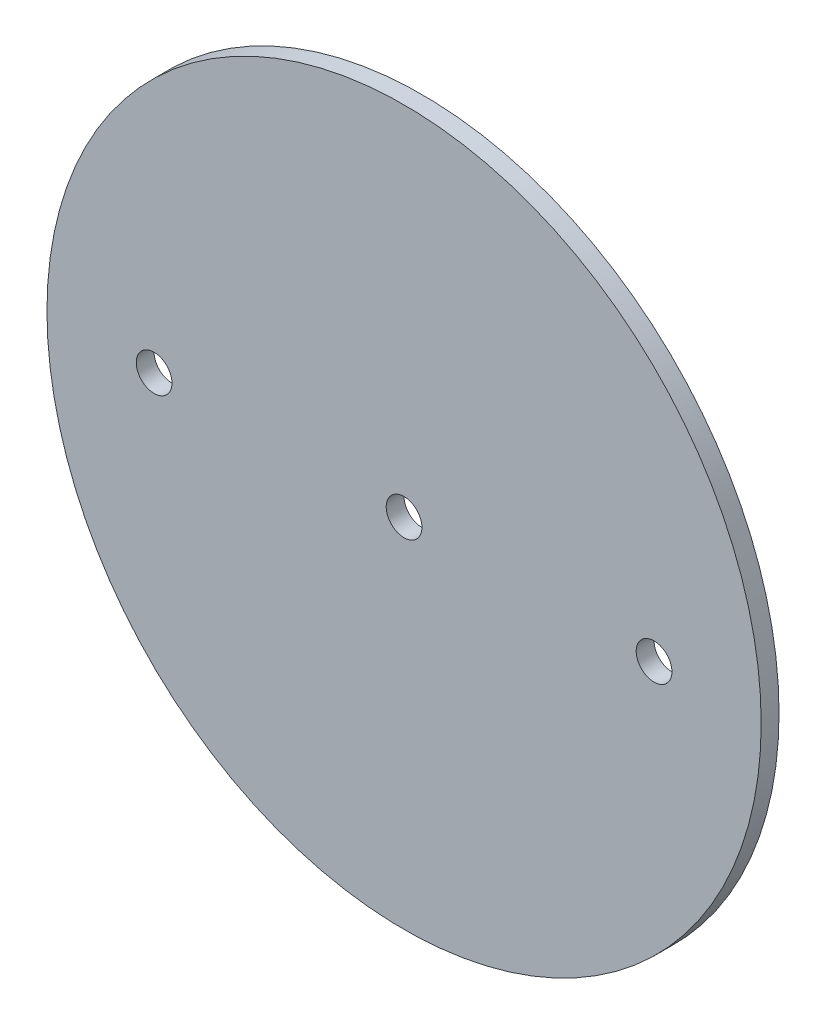
SolidWorks part; units mm, degrees
ref_plane "Front Plane" through (0, 0, 0) normal (0, 0, 1) x (1, 0, 0)
ref_plane "Top Plane" through (0, 0, 0) normal (0, 1, 0) x (1, 0, 0)
ref_plane "Right Plane" through (0, 0, 0) normal (1, 0, 0) x (0, 0, -1)
sketch "Sketch1" plane through (0, 0, 0) normal (0, 0, 1) x (1, 0, 0)
  circle A0 centre (0, 0) radius 63.5
  dimension "D1" = 127
extrude "Boss-Extrude1" add sketch "Sketch1" along normal mid plane 3.175
sketch "Sketch2" plane through (0, 0, 1.5875) normal (0, 0, 1) x (1, 0, 0)
  line L0 (-1000, 0) -> (49000, 0) construction
  point P1 (0, 0)
  point P4 (44.45, 0)
  point P5 (-44.45, 0)
  dimension "D1" = 44.45
  dimension "D2" = 88.9
hole_wizard "1/4 (0.25) Diameter Hole1" positions "Sketch2" profile "Sketch3" hole size "1/4" standard "ANSI Inch" end condition through all
sketch "Sketch3" plane through (-44.45, 0, 1.5875) normal (1, 0, 0) x (0, -1, 0)
  line L0 (0, 0) -> (0, 3.175)
  line L1 (0, 3.175) -> (3.175, 3.175)
  line L2 (3.175, 3.175) -> (3.175, 0)
  line L5 (3.175, 0) -> (0, 0)
  line L11 (0, -6.35) -> (0, 107.95) construction
  dimension "Thru Hole Dia." = 6.35
  dimension "Thru Hole Depth" = 3.175
equation "\"AIRFRAME_OD\"= 5.15in"
equation "\"AIRFRAME_ID\"= 5.00in"
equation "\"FLAT_T\"= 0.125in"
equation "\"NOSE_EXP_L\"= 27in"
equation "\"NOSE_SHOULDER_L\"= 5in"
equation "\"MAIN_L\"= 30in"
equation "\"RECO_COUP_L\"= 10in"
equation "\"RECO_SWITCH_L\"= 2in"
equation "\"DROGUE_L\"= 20in"
equation "\"ATS_FORE_COUP_L\"= 5.5in"
equation "\"ATS_AFT_COUP_L\"= 4.5in"
equation "\"LOWER_L\"= 30in"
equation "\"FIN_N\"= 4"
equation "\"CR_AFT_X\"= 0.5in"
equation "\"CR_FORE_X\"= 9.25in"
equation "\"FIN_ROOT\"= 8in"
equation "\"FIN_X\"= 0.75in"
equation "\"MOTOR_OD\"= 3.091in"
equation "\"MOTOR_ID\"= 3.00in"
equation "\"COUPLER_OD\"= 4.998in"
equation "\"COUPLER_ID\"= 4.88in"
equation "\"D1@Sketch1\"=\"AIRFRAME_ID\""
equation "\"D1@Boss-Extrude1\"=\"FLAT_T\""
equation "\"RECO_ROD_X\"= 3.5in"
equation "\"ATS_ROD_X\"= 3.75in"
equation "\"D1@Sketch2\"=\"RECO_ROD_X\"*0.5"
equation "\"D2@Sketch2\"=\"RECO_ROD_X\""
equation "\"MOTOR_L\"= 14in"
equation "\"MOTOR_LOWER_X\"= 2in"
